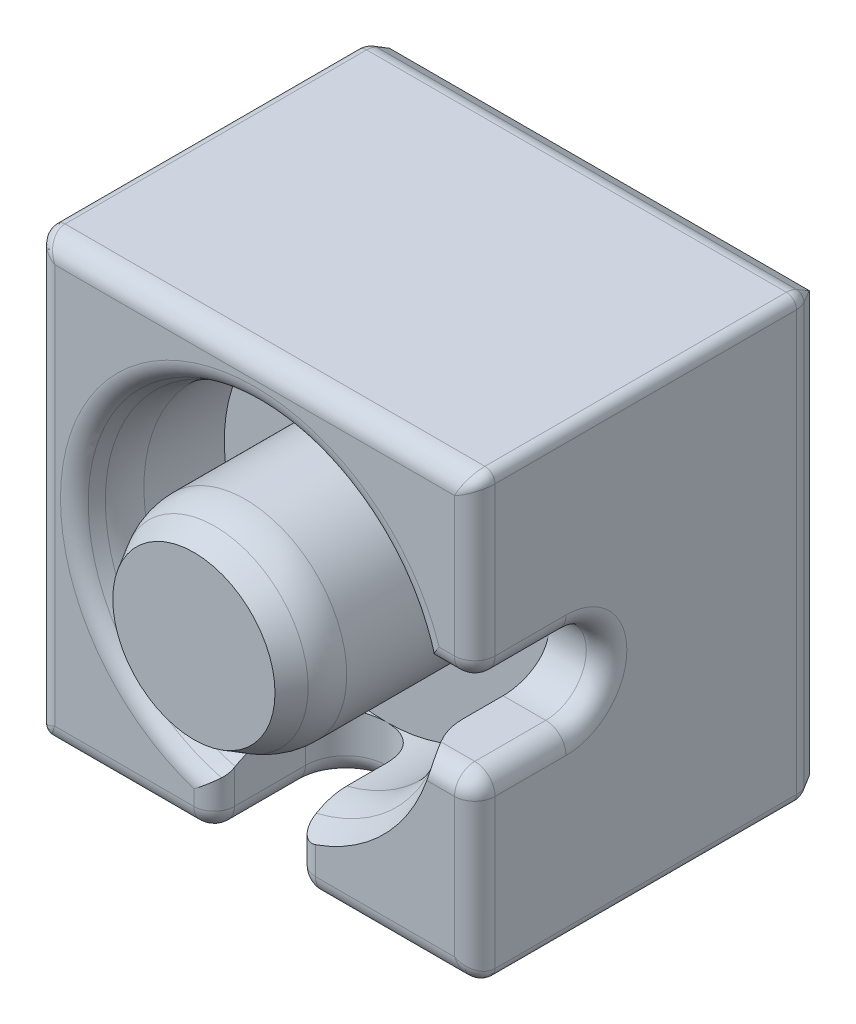
SolidWorks part; units mm, degrees
ref_plane "Ebene vorne" through (0, 0, 0) normal (0, 0, 1) x (1, 0, 0)
ref_plane "Ebene oben" through (0, 0, 0) normal (0, 1, 0) x (1, 0, 0)
ref_plane "Ebene rechts" through (0, 0, 0) normal (1, 0, 0) x (0, 0, -1)
sketch "Skizze1" plane through (0, 0, 0) normal (0, 0, 1) x (1, 0, 0)
  line L1 (-10.85, -10.85) -> (10.85, -10.85)
  line L2 (-10.85, -10.85) -> (-10.85, 10.85)
  line L3 (-10.85, 10.85) -> (10.85, 10.85)
  line L4 (10.85, -10.85) -> (10.85, 10.85)
  line L5 (-10.85, -10.85) -> (10.85, 10.85) construction
  line L6 (-10.85, 10.85) -> (10.85, -10.85) construction
  point P0 (0, 0)
  dimension "D1" = 21.7
  dimension "D2" = 21.7
extrude "Aufsatz-Linear austragen1" add sketch "Skizze1" along normal blind 20
sketch "Skizze2" plane through (0, 0, 20) normal (0, 0, 1) x (1, 0, 0)
  circle A0 centre (0, 0) radius 5
  circle A1 centre (0, 0) radius 8
  dimension "D1" = 10
  dimension "D2" = 16
extrude "Schnitt-Linear austragen1" cut sketch "Skizze2" against normal blind 9.5
fillet "Verrundung1" radius 0.5 4 edges at (-10.85, -10.85, 10) (10.85, -10.85, 10) (-10.85, 10.85, 10) (10.85, 10.85, 10)
sketch "Skizze3" plane through (0, 0, 20) normal (0, 0, 1) x (1, 0, 0)
  line L4 (-10.85, 10.35) -> (-10.85, -10.35)
  line L5 (-10.35, -10.85) -> (10.35, -10.85)
  line L6 (10.85, -10.35) -> (10.85, 10.35)
  line L7 (10.35, 10.85) -> (-10.35, 10.85)
  line L8 (-10.85, 10.35) -> (-10.85, -10.35)
  line L9 (-10.35, -10.85) -> (10.35, -10.85)
  line L10 (10.85, -10.35) -> (10.85, 10.35)
  line L11 (10.35, 10.85) -> (-10.35, 10.85)
  circle A1 centre (0, 0) radius 5
  circle A2 centre (0, 0) radius 5
  arc A4 (-10.85, -10.35) -> (-10.35, -10.85) centre (-10.35, -10.35) ccw
  arc A5 (10.35, -10.85) -> (10.85, -10.35) centre (10.35, -10.35) ccw
  arc A6 (10.85, 10.35) -> (10.35, 10.85) centre (10.35, 10.35) ccw
  arc A7 (-10.35, 10.85) -> (-10.85, 10.35) centre (-10.35, 10.35) ccw
  arc A8 (-10.85, -10.35) -> (-10.35, -10.85) centre (-10.35, -10.35) ccw
  arc A9 (10.35, -10.85) -> (10.85, -10.35) centre (10.35, -10.35) ccw
  arc A10 (10.85, 10.35) -> (10.35, 10.85) centre (10.35, 10.35) ccw
  arc A11 (-10.35, 10.85) -> (-10.85, 10.35) centre (-10.35, 10.35) ccw
  dimension "D1" = 0
  dimension "D2" = 0
extrude "Schnitt-Linear austragen2" cut sketch "Skizze3" against normal blind 3
chamfer "Fase1" distance 1 angle 60 2 edges at (5, 0, 20) (8, 0, 17) first distance on face at (5, 0, 20) first distance on face at (0, 0, 17)
fillet "Verrundung2" radius 3 2 edges at (-5, 0, 18.2679) (8, 0, 15.2679)
sketch "Skizze4" plane through (10.85, 0, 0) normal (1, 0, 0) x (0, 0, -1)
  line L0 (-21.5, 0) -> (-12.5, 0) construction
  line L1 (-17, -10.35) -> (-17, 10.35) construction
  line L2 (-21.5, 2) -> (-12.5, 2)
  line L3 (-21.5, -2) -> (-12.5, -2)
  line L6 (-10.5, 8) -> (-10.5, -8) construction
  arc A0 (-21.5, 2) -> (-21.5, -2) centre (-21.5, 0) ccw
  arc A1 (-12.5, -2) -> (-12.5, 2) centre (-12.5, 0) ccw
  point P5 (-17, 0)
  dimension "D1" = 4
extrude "Schnitt-Linear austragen3" cut sketch "Skizze4" against normal up to next
pattern_circular "Kreismuster1" count 2 over 90 about axis through (0, 0, 10.5) along (0, 0, 1) of "Schnitt-Linear austragen3" reverse direction yes
fillet "Verrundung3" radius 1 6 edges at (10.85, -2, 14.75) (10.85, 2, 14.75) (-2, -10.85, 14.75) (2, -10.85, 14.75) (10.85, 0, 10.5) (0, -10.85, 10.5)
fillet "Verrundung4" radius 1 19 edges at (9.3125, 2, 17) (10.5571, 2.2929, 17) (-2, -9.3125, 17) (-2.2929, -10.5571, 17) (-6.675, -10.85, 17) (-10.7036, -10.7036, 17) (-10.85, 0, 17) (-10.7036, 10.7036, 17) (0, 10.85, 17) (10.7036, 10.7036, 17) (2, -9.3125, 17) (2.2929, -10.5571, 17) (9.3125, -2, 17) (10.5571, -2.2929, 17) (10.85, -6.675, 17) (10.7036, -10.7036, 17) (-6.364, 6.364, 17) (10.85, 6.675, 17) (6.675, -10.85, 17)
chamfer "Fase2" distance 0.5 angle 60 8 edges at (0, 10.85, 0) (-10.7036, 10.7036, 0) (10.7036, 10.7036, 0) (-10.85, 0, 0) (10.85, 0, 0) (-10.7036, -10.7036, 0) (10.7036, -10.7036, 0) (0, -10.85, 0) first distance on face at (0, 0, 0)
fillet "Verrundung5" radius 1 8 edges at (-10.7036, -10.7036, 0.866) (-10.85, 0, 0.866) (-10.7036, 10.7036, 0.866) (0, 10.85, 0.866) (10.7036, 10.7036, 0.866) (10.85, 0, 0.866) (10.7036, -10.7036, 0.866) (0, -10.85, 0.866)
